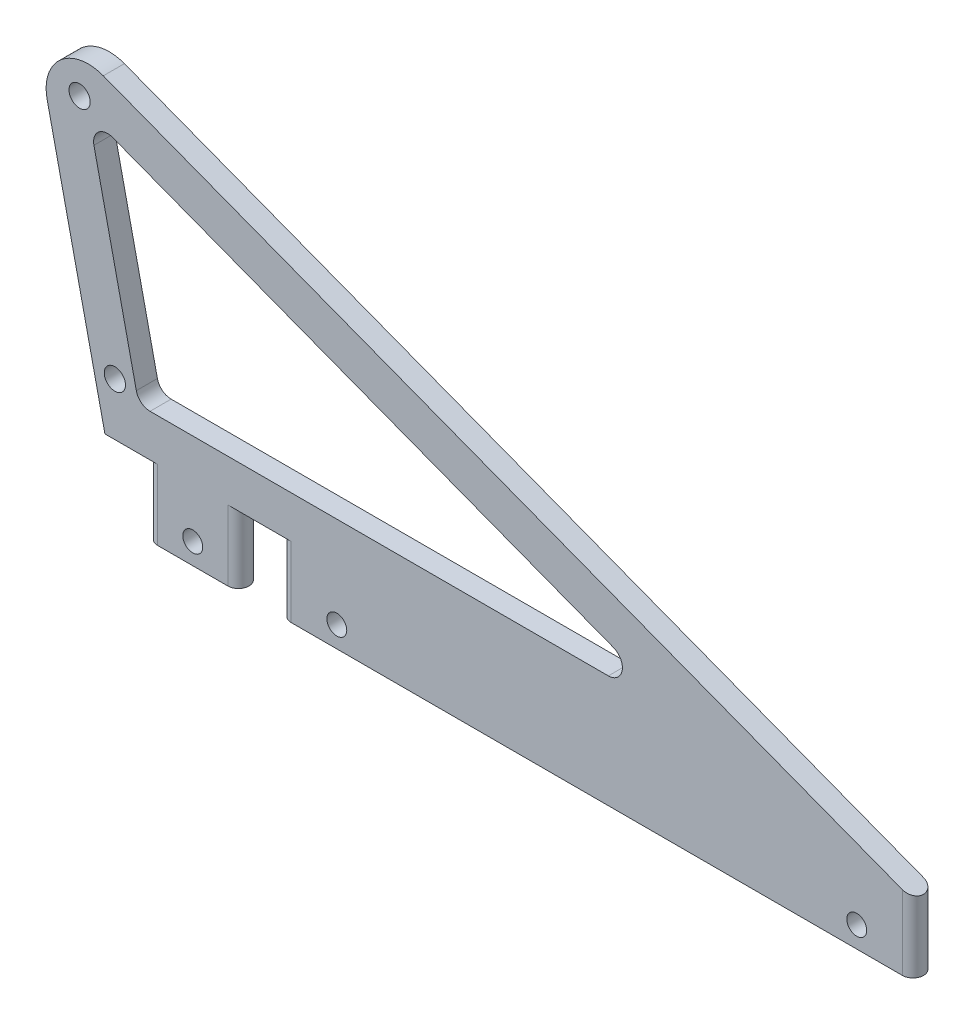
SolidWorks part; units mm, degrees
ref_plane "Front Plane" through (0, 0, 0) normal (0, 0, 1) x (1, 0, 0)
ref_plane "Top Plane" through (0, 0, 0) normal (0, 1, 0) x (1, 0, 0)
ref_plane "Right Plane" through (0, 0, 0) normal (1, 0, 0) x (0, 0, -1)
sketch "Sketch1" plane through (0, 0, 0) normal (0, 0, 1) x (1, 0, 0)
  line L0 (0, 0) -> (9.525, 0)
  line L1 (9.525, 0) -> (9.525, -15.875)
  line L2 (9.525, -15.875) -> (30.1625, -15.875)
  line L3 (30.1625, -15.875) -> (30.1625, 0)
  line L4 (30.1625, 0) -> (39.6875, 0)
  line L5 (39.6875, 0) -> (39.6875, -15.875)
  line L6 (39.6875, -15.875) -> (182.5625, -15.875)
  line L7 (182.5625, -15.875) -> (182.5625, 0)
  line L9 (182.5625, 0) -> (-16.8931, 76.2)
  line L10 (-16.8931, 76.2) -> (0, 0)
  dimension "D1" = 9.525
  dimension "D2" = 20.6375
  dimension "D3" = 9.525
  dimension "D4" = 142.875
  dimension "D5" = 15.875
  dimension "D6" = 76.2
  dimension "D7" = 102.5
extrude "Boss-Extrude1" add sketch "Sketch1" along normal blind 4.7625
sketch "Sketch2" plane through (0, 0, 4.7625) normal (0, 0, 1) x (1, 0, 0)
  line L2 (7.6446, 9.525) -> (130.9411, 9.525)
  line L3 (30.1625, 0) -> (39.6875, 0) construction
  line L4 (-3.7644, 60.9879) -> (9.2992, 2.0616)
  line L5 (179.1632, -8.8978) -> (-3.7644, 60.9879)
  line L6 (-3.7644, 60.9879) -> (7.6446, 9.525)
  line L7 (130.9411, 9.525) -> (-3.7644, 60.9879)
  dimension "D2" = 9.525
  dimension "D1" = 9.525
extrude "Cut-Extrude1" cut sketch "Sketch2" against normal through all
fillet "Fillet1" radius 3.175 3 edges at (7.6446, 9.525, 2.3813) (130.9411, 9.525, 2.3813) (-3.7644, 60.9879, 2.3813)
fillet "Fillet2" radius 9.525 1 edges at (-16.8931, 76.2, 2.3813)
hole_wizard "#12 (0.189) Diameter Hole1" positions "Sketch3" profile "Sketch4" hole size "#12" standard "ANSI Inch" end condition through all
sketch "Sketch3" plane through (0, 0, 4.7625) normal (0, 0, 1) x (1, 0, 0)
  line L0 (-9.9877, 68.1987) -> (-1.4626, 58.3208)
  line L3 (-2.4052, 10.8491) -> (6.894, 12.9107)
  line L4 (-13.0636, 58.9263) -> (0, 0) construction
  line L5 (-2.4879, 55.23) -> (7.0931, 12.0128) construction
  arc A0 (-0.3651, 69.8856) -> (-13.0636, 58.9263) centre (-3.7644, 60.9879) ccw construction
  arc A1 (1.7449, 58.8831) -> (-2.4879, 55.23) centre (0.6118, 55.9172) ccw construction
  point P0 (-5.7252, 63.2598)
  point P16 (2.2444, 11.8799)
  point P37 (1.259, 16.3249)
  dimension "D1" = 11.1125
sketch "Sketch4" plane through (-5.7252, 63.2598, 4.7625) normal (1, 0, 0) x (0, -1, 0)
  line L0 (0, 0) -> (0, 4.7625)
  line L1 (0, 4.7625) -> (2.4003, 4.7625)
  line L2 (2.4003, 4.7625) -> (2.4003, 0)
  line L5 (2.4003, 0) -> (0, 0)
  line L11 (0, -6.35) -> (0, 107.95) construction
  dimension "Thru Hole Dia." = 4.8006
  dimension "Thru Hole Depth" = 4.7625
hole_wizard "#8 Clearance Hole1" positions "Sketch5" profile "Sketch6" hole size "#8" standard "ANSI Inch" end condition through all
sketch "Sketch5" plane through (0, 0, 4.7625) normal (0, 0, 1) x (1, 0, 0)
  line L0 (9.525, -11.1125) -> (30.1625, -11.1125)
  line L1 (9.525, 0) -> (9.525, -15.875) construction
  line L2 (182.5625, -15.875) -> (182.5625, 0) construction
  line L4 (0, 0) -> (9.525, 0) construction
  line L5 (30.1625, -11.1125) -> (182.5625, -11.1125)
  line L6 (30.1625, -15.875) -> (30.1625, 0) construction
  line L7 (39.6875, 0) -> (39.6875, -15.875) construction
  point P0 (19.8438, -11.1125)
  point P2 (52.3875, -11.1125)
  point P4 (169.8625, -11.1125)
  dimension "D1" = 11.1125
  dimension "D2" = 12.7
  dimension "D3" = 12.7
sketch "Sketch6" plane through (19.8438, -11.1125, 4.7625) normal (1, 0, 0) x (0, -1, 0)
  line L0 (0, 0) -> (0, 4.7625)
  line L1 (0, 4.7625) -> (2.2479, 4.7625)
  line L2 (2.2479, 4.7625) -> (2.2479, 0)
  line L5 (2.2479, 0) -> (0, 0)
  line L11 (0, -6.35) -> (0, 107.95) construction
  dimension "Thru Hole Dia." = 4.4958
  dimension "Thru Hole Depth" = 4.7625
fillet "Fillet3" 2 edges at (9.525, -7.9375, 4.7625) (9.525, -7.9375, 0) type full round first side face at (22.0917, -11.1125, 4.7625) second side face at (22.0916, -11.1125, 0) middle face at (9.525, -7.9375, 2.3813)
fillet "Fillet4" 2 edges at (30.1625, -7.9375, 0) (30.1625, -7.9375, 4.7625) type full round first side face at (22.0916, -11.1125, 0) second side face at (22.0917, -11.1125, 4.7625) middle face at (30.1625, -7.9375, 2.3813)
fillet "Fillet5" 2 edges at (39.6875, -7.9375, 4.7625) (39.6875, -7.9375, 0) type full round first side face at (22.0917, -11.1125, 4.7625) second side face at (22.0916, -11.1125, 0) middle face at (39.6875, -7.9375, 2.3813)
fillet "Fillet6" 2 edges at (182.5625, -7.9375, 0) (182.5625, -7.9375, 4.7625) type full round first side face at (22.0916, -11.1125, 0) second side face at (22.0917, -11.1125, 4.7625) middle face at (182.5625, -7.9375, 2.3813)
equation "\"D2@Sketch2\"=\"D1@Sketch2\""
